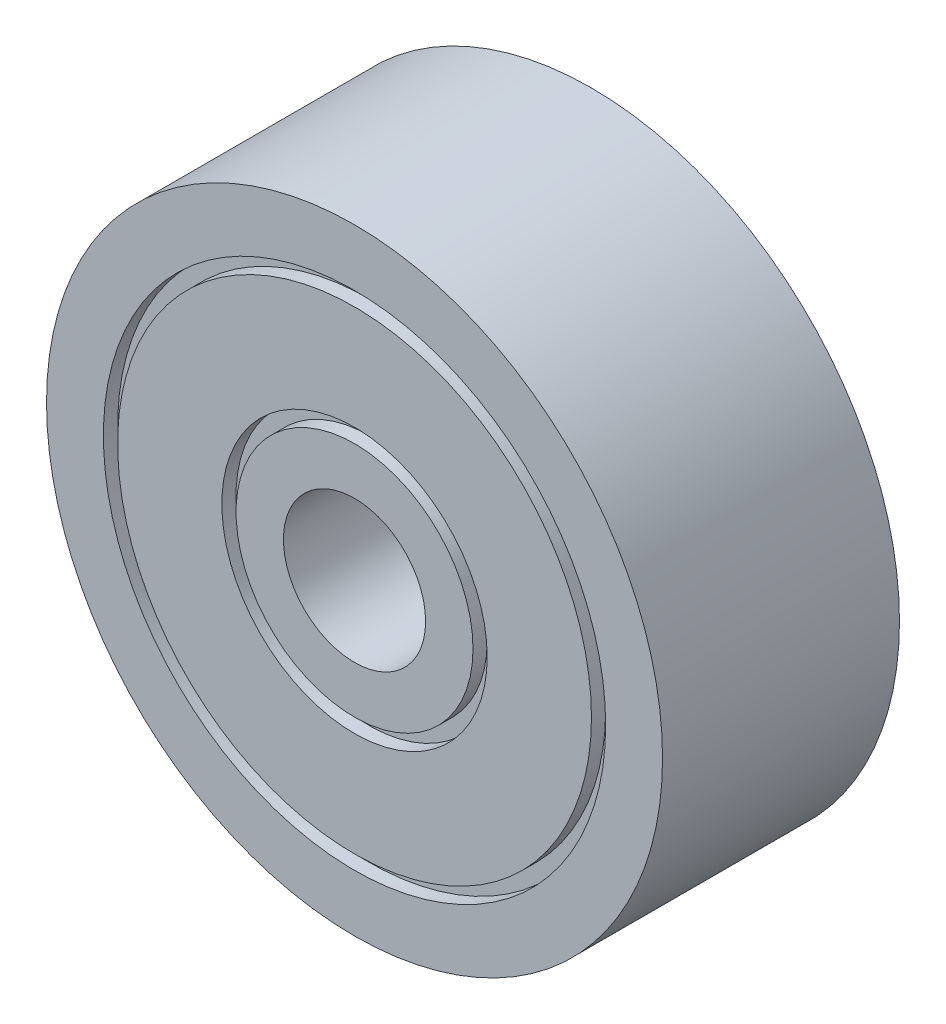
SolidWorks part; units mm, degrees
ref_plane "Front Plane" through (0, 0, 0) normal (0, 0, 1) x (1, 0, 0)
ref_plane "Top Plane" through (0, 0, 0) normal (0, 1, 0) x (1, 0, 0)
ref_plane "Right Plane" through (0, 0, 0) normal (1, 0, 0) x (0, 0, -1)
sketch "Esquisse1" plane through (0, 0, 0) normal (0, 0, 1) x (1, 0, 0)
  circle A0 centre (0, 0) radius 6.5
  circle A1 centre (0, 0) radius 1.5
  dimension "D1" = 13
  dimension "D2" = 3
extrude "Boss.-Extru.1" add sketch "Esquisse1" along normal blind 5
ref_axis "Axe1" through (0, 0, 5.25) along (0, 0, -1)
sketch "Esquisse3" plane through (0, 0, 0) normal (1, 0, 0) x (0, 0, -1)
  line L0 (-5, 6.5) -> (-5, -6.5) construction
  line L1 (-5, 2.8) -> (-4.7, 2.8)
  line L2 (-5, 2.8) -> (-5, 2.5)
  line L3 (-5, 2.5) -> (-4.7, 2.5)
  line L4 (-4.7, 2.8) -> (-4.7, 2.5)
  line L5 (2.75, 0) -> (-2.75, 0) construction
  line L6 (0, 7.15) -> (0, -7.15) construction
  line L7 (-0.3, 2.8) -> (0, 2.8)
  line L8 (-0.3, 2.8) -> (-0.3, 2.5)
  line L9 (-0.3, 2.5) -> (0, 2.5)
  line L10 (0, 2.8) -> (0, 2.5)
  line L12 (-4.7, 5) -> (-5, 5)
  line L13 (-4.7, 5) -> (-4.7, 5.3)
  line L14 (-4.7, 5.3) -> (-5, 5.3)
  line L15 (-5, 5) -> (-5, 5.3)
  line L16 (-0.3, 5) -> (0, 5)
  line L17 (-0.3, 5) -> (-0.3, 5.3)
  line L18 (-0.3, 5.3) -> (0, 5.3)
  line L19 (0, 5) -> (0, 5.3)
  point P22 (0, 0)
  dimension "D1" = 2.5
  dimension "D2" = 0.3
  dimension "D3" = 0.3
  dimension "D4" = 5
revolve "Enlèvement de matière-Révolution1" cut sketch "Esquisse3" angle 360 about axis through (0, 0, 5.25) along (0, 0, -1)
